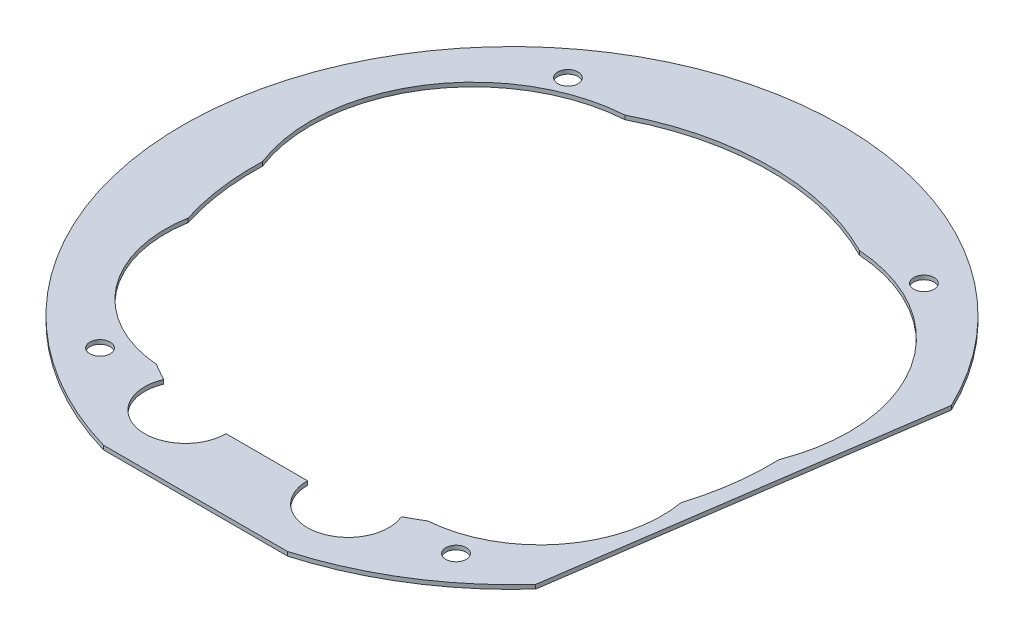
SolidWorks part; units mm, degrees
ref_plane "Front Plane" through (0, 0, 0) normal (0, 0, 1) x (1, 0, 0)
ref_plane "Top Plane" through (0, 0, 0) normal (0, 1, 0) x (1, 0, 0)
ref_plane "Right Plane" through (0, 0, 0) normal (1, 0, 0) x (0, 0, -1)
sketch "Sketch1" plane through (0, 0, 0) normal (0, 1, 0) x (1, 0, 0)
  line L1 (-4, -24.1073) -> (4, -24.1073)
  line L2 (29.2378, 13.961) -> (24.0491, -21.7118)
  line L3 (-9.0608, -31.1073) -> (9.0608, -31.1073)
  arc A0 (11.6854, -22.5524) -> (13.329, -21.6217) centre (0, 0) ccw
  circle A1 centre (-17.5, 23) radius 1
  arc A2 (9.0608, -31.1073) -> (24.0491, -21.7118) centre (0, 0) ccw
  arc A3 (29.2378, 13.961) -> (-9.0608, -31.1073) centre (0, 0) ccw
  circle A4 centre (-17.5, -23) radius 1
  circle A5 centre (17.5, -23) radius 1
  circle A6 centre (17.5, 23) radius 1
  arc A7 (-4, -24.1073) -> (-11.6854, -22.5524) centre (-8, -24.1073) cw
  arc A8 (4, -24.1073) -> (11.6854, -22.5524) centre (8, -24.1073) ccw
  arc A9 (-25.3851, 0.8688) -> (-11.535, 22.6297) centre (-10.4719, 6.6651) cw
  arc A10 (11.535, 22.6297) -> (25.3851, 0.8688) centre (10.4719, 6.6651) cw
  arc A11 (-25.3851, 0.8688) -> (-24.2363, -7.6002) centre (0, 0) ccw
  arc A12 (11.535, 22.6297) -> (-11.535, 22.6297) centre (0, 0) ccw
  arc A13 (-24.2363, -7.6002) -> (-13.329, -21.6217) centre (-12.4138, -9.6566) ccw
  arc A14 (13.329, -21.6217) -> (24.2363, -7.6002) centre (12.4138, -9.6566) ccw
  arc A15 (-13.329, -21.6217) -> (-11.6854, -22.5524) centre (0, 0) ccw
  arc A16 (24.2363, -7.6002) -> (25.3851, 0.8688) centre (0, 0) ccw
  point P33 (0, 0)
  point P34 (13.329, -21.7118)
  dimension "D1" = 2
  dimension "D2" = 2
  dimension "D3" = 2
  dimension "D4" = 2
  dimension "D10" = 7
  dimension "D11" = 25.4
  dimension "D12" = 32.4
  dimension "D15" = 4
  dimension "D16" = 4
  dimension "D20" = 30
  dimension "D21" = 16
  dimension "D22" = 16
  dimension "D24" = 12
  dimension "D26" = 12
  dimension "D27" = 20
  dimension "D5" = 17.5
  dimension "D6" = 23
  dimension "D7" = 46
  dimension "D8" = 35
  dimension "D9" = 7
  dimension "D13" = 16
  dimension "D14" = 36.0481
  dimension "D17" = 8
  dimension "D18" = 7.8411
  dimension "D19" = 7.8411
  dimension "D23" = 30
  dimension "D25" = 20
extrude "Boss-Extrude1" add sketch "Sketch1" along normal blind 0.4
